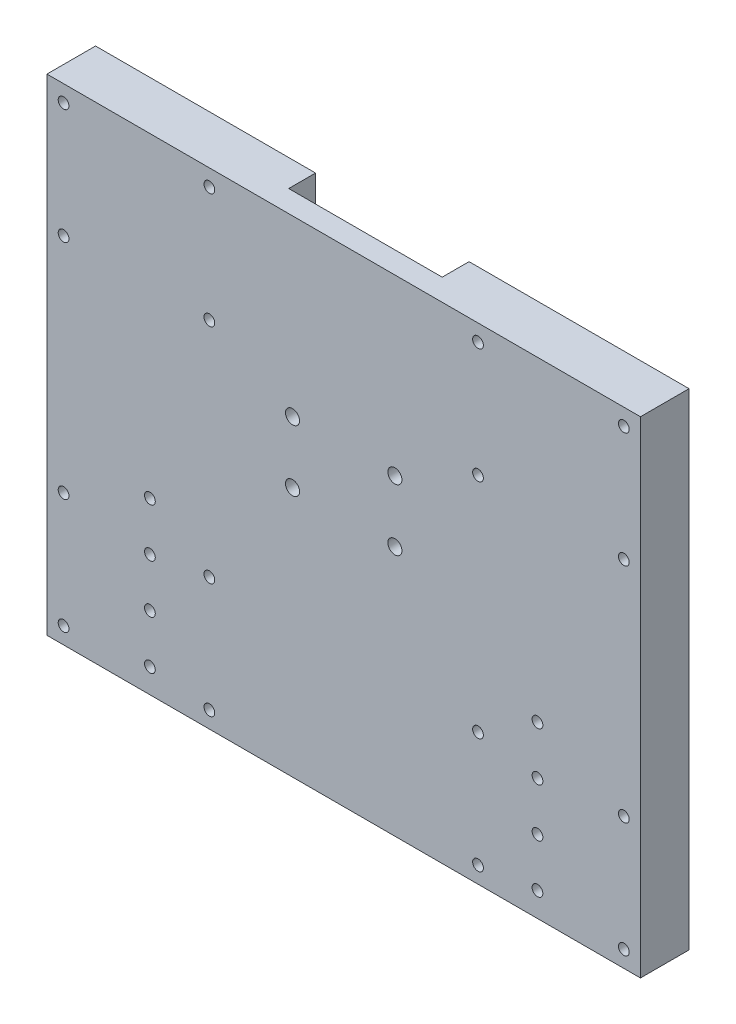
SolidWorks part; units mm, degrees
ref_plane "Piano frontale" through (0, 0, 0) normal (0, 0, 1) x (1, 0, 0)
ref_plane "Piano superiore" through (0, 0, 0) normal (0, 1, 0) x (1, 0, 0)
ref_plane "Piano destro" through (0, 0, 0) normal (1, 0, 0) x (0, 0, -1)
sketch "Schizzo1" plane through (0, 0, 0) normal (0, 0, 1) x (1, 0, 0)
  line L1 (116, -95) -> (-116, -95)
  line L2 (116, -95) -> (116, 95)
  line L3 (116, 95) -> (-116, 95)
  line L4 (-116, -95) -> (-116, 95)
  line L5 (116, -95) -> (-116, 95) construction
  line L6 (116, 95) -> (-116, -95) construction
  point P0 (0, 0)
  dimension "D1" = 232
  dimension "D2" = 190
extrude "Estrusione-Estrusione1" add sketch "Schizzo1" along normal blind 19
sketch "Schizzo3" plane through (0, 0, 19) normal (0, 0, 1) x (1, 0, 0)
  line L0 (20, 7) -> (-20, 7) construction
  line L1 (-20, 7) -> (20, -17) construction
  line L2 (20, -17) -> (20, 7) construction
  line L3 (20, 7) -> (-20, -17) construction
  line L4 (-20, -17) -> (-20, 7) construction
  line L5 (-20, -17) -> (20, -17) construction
  circle A8 centre (20, 7) radius 3
  circle A9 centre (-20, 7) radius 3
  circle A10 centre (-20, -17) radius 3
  circle A11 centre (20, -17) radius 3
  point P21 (0, -5)
  dimension "D1" = 40
  dimension "D2" = 24
sketch "Schizzo4" plane through (0, 95, 0) normal (0, 1, 0) x (1, 0, 0)
  line L0 (116, 0) -> (-116, 0) construction
  line L1 (30, 0) -> (-30, 0)
  line L2 (30, 0) -> (30, -10.5)
  line L3 (30, -10.5) -> (-30, -10.5)
  line L4 (-30, 0) -> (-30, -10.5)
  dimension "D1" = 10.5
extrude "Taglio-Estrusione2" cut sketch "Schizzo4" against normal through all
sketch "Sketch1" plane through (0, 0, 0) normal (0, 0, -1) x (-1, 0, 0)
  point P0 (-109.5, 88.5)
  point P1 (-109.5, 43.5)
  point P3 (-52.5, 88.5)
  point P5 (-52.5, 43.5)
  point P7 (-52.5, -43.5)
  point P9 (-109.5, -43.5)
  point P11 (-109.5, -88.5)
  point P13 (-52.5, -88.5)
  point P15 (52.5, -88.5)
  point P17 (109.5, -88.5)
  point P19 (109.5, -43.5)
  point P21 (52.5, -43.5)
  point P23 (52.5, 43.5)
  point P25 (109.5, 43.5)
  point P27 (109.5, 88.5)
  point P29 (52.5, 88.5)
hole_wizard "Tap Drill for M5 Tap1" positions "Sketch2" profile "Sketch3" hole size "M5" standard "ISO" end condition through all
sketch "Sketch2" plane through (0, 0, 0) normal (0, 0, -1) x (-1, 0, 0)
  point P0 (-109.5, 88.5)
  point P3 (-109.5, 43.5)
  point P6 (-52.5, 43.5)
  point P9 (-52.5, 88.5)
  point P12 (52.5, 88.5)
  point P15 (109.5, 88.5)
  point P18 (109.5, 43.5)
  point P21 (52.5, 43.5)
  point P24 (52.5, -43.5)
  point P27 (109.5, -43.5)
  point P30 (109.5, -88.5)
  point P33 (52.5, -88.5)
  point P36 (-52.5, -88.5)
  point P39 (-52.5, -43.5)
  point P42 (-109.5, -43.5)
  point P45 (-109.5, -88.5)
sketch "Sketch3" plane through (109.5, 88.5, 0) normal (1, 0, 0) x (0, 1, 0)
  line L0 (0, 0) -> (0, 19)
  line L1 (0, 19) -> (2.1, 19)
  line L2 (2.1, 19) -> (2.1, 0)
  line L5 (2.1, 0) -> (0, 0)
  line L11 (0, -6.35) -> (0, 107.95) construction
  dimension "Thru Hole Dia." = 4.2
  dimension "Thru Hole Depth" = 19
hole_wizard "M5 Clearance Hole1" positions "Sketch4" profile "Sketch5" hole size "M5" standard "ISO" end condition through all
sketch "Sketch4" plane through (0, 0, 19) normal (0, 0, 1) x (1, 0, 0)
  point P0 (-20, 27)
  point P3 (20, 27)
  point P6 (20, 3)
  point P9 (-20, 3)
sketch "Sketch5" plane through (-20, 27, 19) normal (1, 0, 0) x (0, -1, 0)
  line L0 (0, 0) -> (0, 19)
  line L1 (0, 19) -> (2.75, 19)
  line L2 (2.75, 19) -> (2.75, 0)
  line L5 (2.75, 0) -> (0, 0)
  line L11 (0, -6.35) -> (0, 107.95) construction
  dimension "Thru Hole Dia." = 5.5
  dimension "Thru Hole Depth" = 19
hole_wizard "Tap Drill for M5 Tap3" positions "Sketch6" profile "Sketch7" hole size "M5" standard "ISO" end condition up to next
sketch "Sketch6" plane through (0, 0, 19) normal (0, 0, 1) x (1, 0, 0)
  point P0 (-75.75, -28.5)
  point P2 (-75.75, -47.5)
  point P4 (-75.75, -66.5)
  point P6 (-75.75, -85.5)
  point P8 (75.75, -28.5)
  point P10 (75.75, -47.5)
  point P12 (75.75, -66.5)
  point P14 (75.75, -85.5)
sketch "Sketch7" plane through (-75.75, -28.5, 19) normal (1, 0, 0) x (0, -1, 0)
  line L0 (0, 0) -> (0, 19)
  line L1 (0, 19) -> (2.1, 19)
  line L2 (2.1, 19) -> (2.1, 0)
  line L5 (2.1, 0) -> (0, 0)
  line L11 (0, -6.35) -> (0, 107.95) construction
  dimension "Thru Hole Dia." = 4.2
  dimension "Thru Hole Depth" = 19
